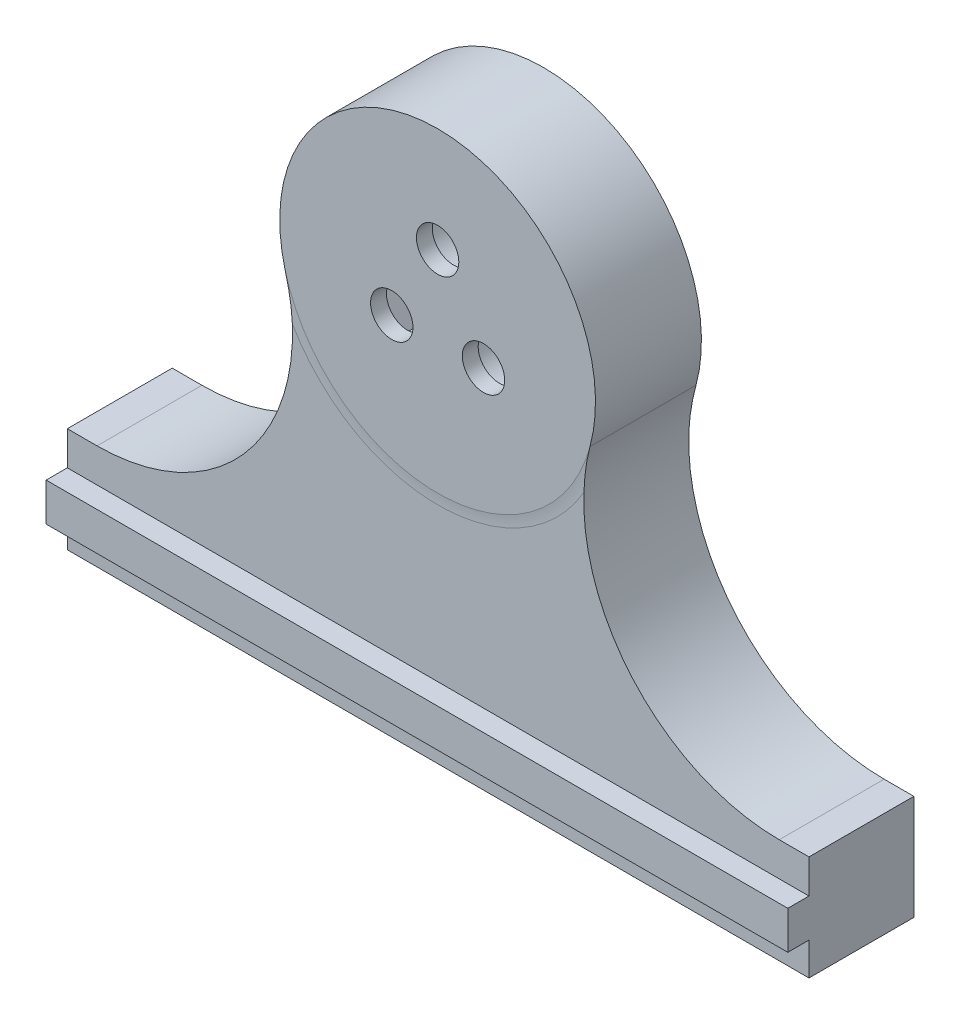
SolidWorks part; units mm, degrees
ref_plane "Front Plane" through (0, 0, 0) normal (0, 0, 1) x (1, 0, 0)
ref_plane "Top Plane" through (0, 0, 0) normal (0, 1, 0) x (1, 0, 0)
ref_plane "Right Plane" through (0, 0, 0) normal (1, 0, 0) x (0, 0, -1)
sketch "Sketch1" plane through (0, 0, 0) normal (0, 0, 1) x (1, 0, 0)
  circle A0 centre (0, 0) radius 12.9
  arc A1 (20.4, 0) -> (-20.4, 0) centre (0, 0) ccw
  arc A2 (-20.4, 0) -> (20.4, 0) centre (0, 0) ccw
sketch "Sketch2" plane through (0, 0, 0) normal (0, 0, 1) x (1, 0, 0)
  line L0 (32.9709, -2.3492) -> (31.2709, -2.3492)
  line L1 (31.2709, -11.6478) -> (31.2709, -17.7292)
  line L2 (31.2709, -17.7292) -> (32.9709, -17.7292)
  line L3 (32.9709, -17.7292) -> (32.9709, -2.3492)
  line L4 (31.2709, -2.3492) -> (31.2709, -8.4306)
  arc A0 (31.2709, -11.6478) -> (31.2709, -8.4306) centre (28.6209, -10.0392) ccw
  arc A1 (31.2709, -8.4306) -> (31.2709, -11.6478) centre (28.6209, -10.0392) ccw
sketch "Sketch3" plane through (0, 0, 0) normal (0, 0, 1) x (1, 0, 0)
  line L0 (31.2709, -2.3492) -> (31.2709, -8.4306) construction
  line L1 (31.2709, -11.6478) -> (31.2709, -17.7292) construction
  line L2 (31.2709, -17.7292) -> (32.9709, -17.7292) construction
  line L3 (32.9709, -17.7292) -> (32.9709, -2.3492) construction
  line L4 (32.9709, -2.3492) -> (31.2709, -2.3492) construction
  line L5 (31.2709, -2.3492) -> (31.2709, -8.4306)
  line L6 (31.2709, -11.6478) -> (31.2709, -17.7292)
  line L7 (31.2709, -17.7292) -> (32.9709, -17.7292)
  line L8 (32.9709, -17.7292) -> (32.9709, -2.3492)
  line L9 (32.9709, -2.3492) -> (31.2709, -2.3492)
  line L10 (1.6086, 7.65) -> (7.69, 7.65)
  line L11 (-7.69, 9.35) -> (7.69, 9.35)
  line L12 (-7.69, 9.35) -> (-7.69, 7.65)
  line L13 (-7.69, 7.65) -> (-1.6086, 7.65)
  line L14 (7.69, 9.35) -> (7.69, 7.65)
  line L15 (11.9423, 1.9847) -> (10.4701, 2.8347)
  line L16 (10.4701, 2.8347) -> (7.4294, -2.4319)
  line L17 (5.8208, -5.2181) -> (2.7801, -10.4847)
  line L18 (4.2523, -11.3347) -> (2.7801, -10.4847)
  line L19 (11.9423, 1.9847) -> (4.2523, -11.3347)
  line L20 (-4.2523, -11.3347) -> (-2.7801, -10.4847)
  line L21 (-2.7801, -10.4847) -> (-5.8208, -5.2181)
  line L22 (-7.4294, -2.4319) -> (-10.4701, 2.8347)
  line L23 (-11.9423, 1.9847) -> (-10.4701, 2.8347)
  line L24 (-4.2523, -11.3347) -> (-11.9423, 1.9847)
  circle A0 centre (0, 0) radius 5 construction
  arc A2 (31.2709, -8.4306) -> (31.2709, -11.6478) centre (28.6209, -10.0392) ccw construction
  arc A3 (-1.6086, 7.65) -> (1.6086, 7.65) centre (0, 5) ccw construction
  circle A4 centre (4.3301, -2.5) radius 3.1 construction
  circle A5 centre (-4.3301, -2.5) radius 3.1 construction
  arc A6 (31.2709, -11.6478) -> (31.2709, -8.4306) centre (28.6209, -10.0392) ccw construction
  arc A7 (31.2709, -8.4306) -> (31.2709, -11.6478) centre (28.6209, -10.0392) ccw
  arc A8 (31.2709, -11.6478) -> (31.2709, -8.4306) centre (28.6209, -10.0392) ccw
  arc A9 (-1.6086, 7.65) -> (1.6086, 7.65) centre (0, 5) ccw
  arc A10 (7.4294, -2.4319) -> (5.8208, -5.2181) centre (4.3301, -2.5) ccw
  arc A11 (-5.8208, -5.2181) -> (-7.4294, -2.4319) centre (-4.3301, -2.5) ccw
  point P18 (0, 0)
  point P23 (0, 9.35)
  point P43 (0, 0)
  dimension "D1" = 3
  dimension "D5" = 3
sketch "Sketch4" plane through (0, 0, 0) normal (0, 0, 1) x (1, 0, 0)
  line L0 (11.9423, 1.9847) -> (4.2523, -11.3347) construction
  line L1 (4.2523, -11.3347) -> (2.7801, -10.4847) construction
  line L2 (5.8208, -5.2181) -> (2.7801, -10.4847) construction
  line L3 (10.4701, 2.8347) -> (7.4294, -2.4319) construction
  line L4 (11.9423, 1.9847) -> (10.4701, 2.8347) construction
  line L5 (-7.4294, -2.4319) -> (-10.4701, 2.8347) construction
  line L6 (-11.9423, 1.9847) -> (-10.4701, 2.8347) construction
  line L7 (-4.2523, -11.3347) -> (-11.9423, 1.9847) construction
  line L8 (-4.2523, -11.3347) -> (-2.7801, -10.4847) construction
  line L9 (-2.7801, -10.4847) -> (-5.8208, -5.2181) construction
  line L10 (-7.69, 9.35) -> (7.69, 9.35) construction
  line L11 (7.69, 9.35) -> (7.69, 7.65) construction
  line L12 (1.6086, 7.65) -> (7.69, 7.65) construction
  line L13 (-7.69, 7.65) -> (-1.6086, 7.65) construction
  line L14 (-7.69, 9.35) -> (-7.69, 7.65) construction
  line L15 (11.9423, 1.9847) -> (4.2523, -11.3347)
  line L16 (4.2523, -11.3347) -> (2.7801, -10.4847)
  line L17 (5.8208, -5.2181) -> (2.7801, -10.4847)
  line L18 (10.4701, 2.8347) -> (7.4294, -2.4319)
  line L19 (11.9423, 1.9847) -> (10.4701, 2.8347)
  line L20 (-7.4294, -2.4319) -> (-10.4701, 2.8347)
  line L21 (-11.9423, 1.9847) -> (-10.4701, 2.8347)
  line L22 (-4.2523, -11.3347) -> (-11.9423, 1.9847)
  line L23 (-4.2523, -11.3347) -> (-2.7801, -10.4847)
  line L24 (-2.7801, -10.4847) -> (-5.8208, -5.2181)
  line L25 (-7.69, 9.35) -> (7.69, 9.35)
  line L26 (7.69, 9.35) -> (7.69, 7.65)
  line L27 (1.6086, 7.65) -> (7.69, 7.65)
  line L28 (-7.69, 7.65) -> (-1.6086, 7.65)
  line L29 (-7.69, 9.35) -> (-7.69, 7.65)
  line L30 (-4.3301, -2.5) -> (-8.0973, -4.675) construction
  circle A0 centre (-4.3301, -2.5) radius 2
  circle A1 centre (4.3301, -2.5) radius 2
  circle A2 centre (0, 5) radius 2
  circle A3 centre (0, 0) radius 12.9 construction
  arc A4 (7.4294, -2.4319) -> (5.8208, -5.2181) centre (4.3301, -2.5) ccw construction
  arc A5 (-5.8208, -5.2181) -> (-7.4294, -2.4319) centre (-4.3301, -2.5) ccw construction
  arc A6 (-1.6086, 7.65) -> (1.6086, 7.65) centre (0, 5) ccw construction
  circle A7 centre (0, 0) radius 12.9 construction
  arc A8 (7.4294, -2.4319) -> (5.8208, -5.2181) centre (4.3301, -2.5) ccw
  arc A9 (-5.8208, -5.2181) -> (-7.4294, -2.4319) centre (-4.3301, -2.5) ccw
  arc A10 (-1.6086, 7.65) -> (1.6086, 7.65) centre (0, 5) ccw
  circle A11 centre (0, 0) radius 14.9
  dimension "D1" = 4
  dimension "D3" = 15.38
  dimension "D2" = 2
extrude "Boss-Extrude1" add sketch "Sketch4" along normal blind 1.5 contours A11 A8 L18 L19 L15 L16 L17 A9 L24 L23 L22 L21 L20 A10 L28 L29 L25 L26 L27 | L28 A10 L27 L26 L25 L29 A2 | L24 A9 L20 L21 L22 L23 A0 | L18 A8 L17 L16 L15 L19 A1 region at (6.126, -3.5369, 0) region at (-6.126, -3.5369, 0) region at (0, 7.0737, 0) region at (0, 0, 0)
extrude "Boss-Extrude2" add sketch "Sketch4<3>" against normal blind 8.5 contours A11 A8 L18 L19 L15 L16 L17 A9 L24 L23 L22 L21 L20 A10 L28 L29 L25 L26 L27 region at (0, 0, 0)
sketch "Sketch4<3>" plane through (0, 0, 0) normal (0, 0, 1) x (1, 0, 0) same geometry as "Sketch4"
sketch "Sketch5" plane through (0, 0, 0) normal (1, 0, 0) x (0, 0, -1)
  line L0 (8.45, -37.05) -> (-1.45, -37.05)
  line L1 (8.45, -27.15) -> (-1.45, -27.15)
  line L2 (-1.5, -14.9) -> (8.5, -14.9) construction
  line L3 (-1.5, -14.9) -> (8.5, -14.9)
  line L4 (3.5, -14.9) -> (3.5, -37.05) construction
  line L5 (-1.45, -14.9) -> (-1.45, -30.35)
  line L6 (8.45, -14.9) -> (8.45, -37.05)
  line L7 (8.45, -32.15) -> (-3.45, -32.15) construction
  line L13 (-1.45, -33.95) -> (-1.45, -37.05)
  line L14 (-1.45, -33.95) -> (-3.45, -33.95)
  line L15 (-3.45, -30.35) -> (-3.45, -33.95)
  line L16 (-1.45, -30.35) -> (-3.45, -30.35)
  line L17 (-1.45, -14.9) -> (-1.45, -37.05) construction
  dimension "D3" = 2
  dimension "D4" = 3.6
  dimension "D1" = 4.95
  dimension "D2" = 4.95
sketch "Sketch6" plane through (0, 0, 0) normal (1, 0, 0) x (0, 0, -1)
  line L0 (-1.45, -14.9) -> (-1.45, -30.35) construction
  line L1 (-1.45, -30.35) -> (-3.45, -30.35) construction
  line L2 (-3.45, -30.35) -> (-3.45, -33.95) construction
  line L3 (-1.45, -33.95) -> (-3.45, -33.95) construction
  line L4 (-1.45, -33.95) -> (-1.45, -37.05) construction
  line L5 (8.45, -37.05) -> (-1.45, -37.05) construction
  line L6 (8.45, -14.9) -> (8.45, -37.05) construction
  line L7 (8.45, -27.15) -> (-1.45, -27.15) construction
  line L8 (-1.45, -27.15) -> (-1.45, -30.35)
  line L9 (-1.45, -30.35) -> (-3.45, -30.35)
  line L10 (-3.45, -30.35) -> (-3.45, -33.95)
  line L11 (-1.45, -33.95) -> (-3.45, -33.95)
  line L12 (-1.45, -33.95) -> (-1.45, -37.05)
  line L13 (8.45, -37.05) -> (-1.45, -37.05)
  line L14 (8.45, -27.15) -> (8.45, -37.05)
  line L15 (8.45, -27.15) -> (-1.45, -27.15)
extrude "Boss-Extrude3" add sketch "Sketch6" along normal mid plane 70 separate body
ref_plane "Plane1" through (0, 0, -3.5) normal (0, 0, 1) x (1, 0, 0)
sketch "Sketch8" plane through (0, 0, -3.5) normal (0, 0, 1) x (1, 0, 0)
  line L0 (35, -27.15) -> (-35, -27.15) construction
  line L1 (32.1952, -27.15) -> (-32.1952, -27.15)
  line L2 (-2.3301, -2.5) -> (2.3301, -2.5) construction
  line L3 (0, -2.5) -> (0, -14.9) construction
  circle A0 centre (0, 0) radius 14.9 construction
  arc A2 (-32.1952, -27.15) -> (-14.3841, -3.887) centre (-32.1952, -8.7) ccw
  arc A3 (14.3841, -3.887) -> (32.1952, -27.15) centre (32.1952, -8.7) ccw
  circle A4 centre (-4.3301, -2.5) radius 2 construction
  circle A5 centre (4.3301, -2.5) radius 2 construction
  arc A6 (-14.3841, -3.887) -> (14.3841, -3.887) centre (0, 0) ccw
  point P19 (0, -8.7)
extrude "Boss-Extrude4" add sketch "Sketch8" along normal mid plane 9.9
fillet "Fillet1" radius 10 2 edges at (0, -14.9, -8.45) (0, -14.9, 1.45)
sketch "Sketch9" plane through (0, 0, -8.5) normal (0, 0, -1) x (-1, 0, 0)
  line L0 (-7.4294, -2.4319) -> (-10.4701, 2.8347) construction
  line L1 (-10.4701, 2.8347) -> (-11.9423, 1.9847) construction
  line L2 (-11.9423, 1.9847) -> (-4.2523, -11.3347) construction
  line L3 (-4.2523, -11.3347) -> (-2.7801, -10.4847) construction
  line L4 (-2.7801, -10.4847) -> (-5.8208, -5.2181) construction
  line L5 (5.8208, -5.2181) -> (2.7801, -10.4847) construction
  line L6 (2.7801, -10.4847) -> (4.2523, -11.3347) construction
  line L7 (4.2523, -11.3347) -> (11.9423, 1.9847) construction
  line L8 (11.9423, 1.9847) -> (10.4701, 2.8347) construction
  line L9 (10.4701, 2.8347) -> (7.4294, -2.4319) construction
  line L10 (1.6086, 7.65) -> (7.69, 7.65) construction
  line L11 (7.69, 7.65) -> (7.69, 9.35) construction
  line L12 (7.69, 9.35) -> (-7.69, 9.35) construction
  line L13 (-7.69, 9.35) -> (-7.69, 7.65) construction
  line L14 (-7.69, 7.65) -> (-1.6086, 7.65) construction
  line L15 (-7.4294, -2.4319) -> (-10.4701, 2.8347) construction
  line L16 (-10.4701, 2.8347) -> (-11.9423, 1.9847) construction
  line L17 (-11.9423, 1.9847) -> (-4.2523, -11.3347) construction
  line L18 (-4.2523, -11.3347) -> (-2.7801, -10.4847) construction
  line L19 (-2.7801, -10.4847) -> (-5.8208, -5.2181) construction
  line L20 (5.8208, -5.2181) -> (2.7801, -10.4847) construction
  line L21 (2.7801, -10.4847) -> (4.2523, -11.3347) construction
  line L22 (4.2523, -11.3347) -> (11.9423, 1.9847) construction
  line L23 (11.9423, 1.9847) -> (10.4701, 2.8347) construction
  line L24 (10.4701, 2.8347) -> (7.4294, -2.4319) construction
  line L25 (1.6086, 7.65) -> (7.69, 7.65) construction
  line L26 (7.69, 7.65) -> (7.69, 9.35) construction
  line L27 (7.69, 9.35) -> (-7.69, 9.35) construction
  line L28 (-7.69, 9.35) -> (-7.69, 7.65) construction
  line L29 (-7.69, 7.65) -> (-1.6086, 7.65) construction
  line L30 (7.89, 9.55) -> (-7.89, 9.55)
  line L31 (-7.89, 9.55) -> (-7.89, 7.45)
  line L32 (-7.89, 7.45) -> (-2.2108, 7.45)
  line L33 (2.2108, 7.45) -> (7.89, 7.45)
  line L34 (7.89, 7.45) -> (7.89, 9.55)
  line L35 (-7.5573, -1.8104) -> (-10.3969, 3.1079)
  line L36 (-10.3969, 3.1079) -> (-12.2155, 2.0579)
  line L37 (-12.2155, 2.0579) -> (-4.3255, -11.6079)
  line L38 (-4.3255, -11.6079) -> (-2.5069, -10.5579)
  line L39 (-2.5069, -10.5579) -> (-5.3465, -5.6396)
  line L40 (5.3465, -5.6396) -> (2.5069, -10.5579)
  line L41 (2.5069, -10.5579) -> (4.3255, -11.6079)
  line L42 (4.3255, -11.6079) -> (12.2155, 2.0579)
  line L43 (12.2155, 2.0579) -> (10.3969, 3.1079)
  line L44 (10.3969, 3.1079) -> (7.5573, -1.8104)
  arc A0 (-5.8208, -5.2181) -> (-7.4294, -2.4319) centre (-4.3301, -2.5) ccw construction
  arc A1 (7.4294, -2.4319) -> (5.8208, -5.2181) centre (4.3301, -2.5) ccw construction
  arc A2 (-1.6086, 7.65) -> (1.6086, 7.65) centre (0, 5) ccw construction
  arc A3 (-5.8208, -5.2181) -> (-7.4294, -2.4319) centre (-4.3301, -2.5) ccw construction
  arc A4 (7.4294, -2.4319) -> (5.8208, -5.2181) centre (4.3301, -2.5) ccw construction
  arc A5 (-1.6086, 7.65) -> (1.6086, 7.65) centre (0, 5) ccw construction
  arc A6 (-2.2108, 7.45) -> (2.2108, 7.45) centre (0, 5) ccw
  arc A7 (-5.3465, -5.6396) -> (-7.5573, -1.8104) centre (-4.3301, -2.5) ccw
  arc A8 (7.5573, -1.8104) -> (5.3465, -5.6396) centre (4.3301, -2.5) ccw
  dimension "D1" = 0.2
extrude "Cut-Extrude1" cut sketch "Sketch9" against normal blind 8.5
sketch "Sketch10" plane through (0, 0, 1.5) normal (0, 0, 1) x (1, 0, 0)
  line L0 (0, 0) -> (0, -37.05) construction
  line L1 (35, -37.05) -> (-35, -37.05) construction
sketch "Sketch11" plane through (-35, 0, 0) normal (-1, 0, 0) x (0, 0, 1)
  line L8 (3.45, -30.35) -> (1.45, -30.35)
  line L9 (1.45, -30.35) -> (1.45, -27.15)
  line L10 (1.45, -27.15) -> (-8.45, -27.15)
  line L11 (-8.45, -27.15) -> (-8.45, -37.05)
  line L12 (-8.45, -37.05) -> (1.45, -37.05)
  line L13 (1.45, -37.05) -> (1.45, -33.95)
  line L14 (1.45, -33.95) -> (3.45, -33.95)
  line L15 (3.45, -33.95) -> (3.45, -30.35)
  line L16 (3.45, -30.35) -> (1.45, -30.35)
  line L17 (1.45, -30.35) -> (1.45, -27.15)
  line L18 (1.45, -27.15) -> (-8.45, -27.15)
  line L19 (-8.45, -27.15) -> (-8.45, -37.05)
  line L20 (-8.45, -37.05) -> (1.45, -37.05)
  line L21 (1.45, -37.05) -> (1.45, -33.95)
  line L22 (1.45, -33.95) -> (3.45, -33.95)
  line L23 (3.45, -33.95) -> (3.45, -30.35)
  dimension "D1" = 0
